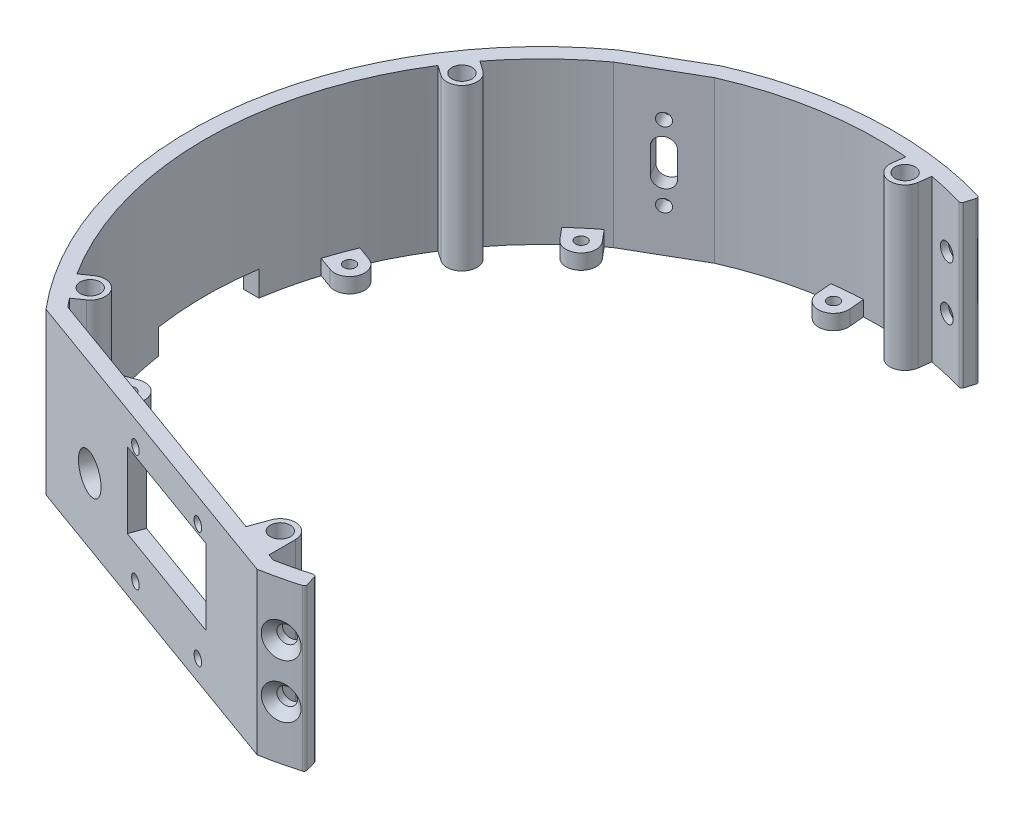
SolidWorks part; units mm, degrees
ref_plane "Front Plane" through (0, 0, 0) normal (0, 0, 1) x (1, 0, 0)
ref_plane "Top Plane" through (0, 0, 0) normal (0, 1, 0) x (1, 0, 0)
ref_plane "Right Plane" through (0, 0, 0) normal (1, 0, 0) x (0, 0, -1)
sketch "Sketch2" plane through (0, 0, 0) normal (0, 1, 0) x (1, 0, 0)
  line L0 (12.3, 68.9109) -> (12.3, -68.9109) construction
  line L1 (12.3, -68.9109) -> (-53.5286, -45.1076)
  line L2 (-28.3033, 64.0228) -> (-41.2937, 56.5228)
  line L3 (-51.7436, -42.5629) -> (12.3, -65.7208)
  line L4 (20.0782, 67.0587) -> (0, 0) construction
  line L5 (0, 0) -> (20.0782, -67.0587) construction
  line L6 (19.2177, 64.1847) -> (20.0782, 67.0587)
  line L7 (20.0782, -67.0587) -> (19.178, -64.0524)
  line L8 (-39.6526, 54.0062) -> (-26.9445, 61.3433)
  line L9 (-34.7985, 60.2728) -> (0, 0) construction
  line L10 (0, 0) -> (0, 50000) construction
  arc A0 (12.3, 68.9109) -> (-28.3033, 64.0228) centre (0, 0) ccw construction
  arc A1 (-53.5286, -45.1076) -> (-41.2937, 56.5228) centre (0, 0) cw
  arc A2 (12.3, 65.8613) -> (-26.9445, 61.3433) centre (0, 0) ccw
  arc A3 (12.3, 68.9109) -> (20.0782, 67.0587) centre (0, 0) cw
  arc A4 (12.3, 65.8613) -> (19.2177, 64.1847) centre (0, 0) cw
  arc A5 (12.3, -68.9109) -> (20.0782, -67.0587) centre (0, 0) ccw
  arc A6 (12.3, -65.7208) -> (19.178, -64.0524) centre (0, 0) ccw
  arc A7 (-39.6526, 54.0062) -> (-51.7436, -42.5629) centre (0, 0) ccw
  arc A8 (-41.2937, 56.5228) -> (12.3, -68.9109) centre (0, 0) ccw construction
  arc A9 (-28.3033, 64.0228) -> (12.3, 68.9109) centre (0, 0) cw
  point P18 (-33.2985, 57.6747)
  dimension "D1" = 70
  dimension "D4" = 3
  dimension "D6" = 8
  dimension "D2" = 12.3
  dimension "D3" = 3
  dimension "D5" = 70
  dimension "D7" = 8
  dimension "D8" = 3
  dimension "D9" = 15
  dimension "D10" = 30
extrude "Boss-Extrude1" add sketch "Sketch2" along normal blind 32
sketch "Sketch3" plane through (0, 0, 0) normal (0, 1, 0) x (1, 0, 0)
  line L0 (12.3, 68.9109) -> (12.3, -68.9109) construction
  line L1 (20.0782, -67.0587) -> (19.178, -64.0524) construction
  line L2 (19.2177, 64.1847) -> (20.0782, 67.0587) construction
  circle A0 centre (0, 0) radius 70 construction
  arc A1 (12.3, -68.9109) -> (20.0782, -67.0587) centre (0, 0) ccw
  arc A2 (12.3, 68.9109) -> (20.0782, 67.0587) centre (0, 0) cw
  point P8 (16.2155, -68.0959)
  point P9 (16.2155, 68.0959)
  dimension "D2" = 140
  dimension "D1" = 12.3
sketch3d "3DSketch1"
  line L0 (16.2155, 0, 68.0959) -> (16.2155, 32, 68.0959)
  line L1 (16.2155, 0, -68.0959) -> (16.2155, 32, -68.0959)
  arc A0 (12.3, 32, 68.9109) -> (20.0782, 32, 67.0587) centre (0, 32, 0) ccw construction
  arc A1 (20.0782, 32, -67.0587) -> (-28.3033, 32, -64.0228) centre (0, 32, 0) ccw construction
  point P6 (0, 102, 0)
  point P13 (0, 102, 0)
  point P14 (16.2155, 21.3333, 68.0959)
  point P15 (16.2155, 10.6667, 68.0959)
  point P16 (16.2155, 10.6667, -68.0959)
  point P17 (16.2155, 21.3333, -68.0959)
  dimension "D1" = 10.6667
  dimension "D2" = 21.3333
  dimension "D3" = 10.6667
  dimension "D4" = 21.3333
ref_plane "Plane1" through (16.2155, 0, -68.0959) normal (0.2317, 0, -0.9728) x (-0.9728, 0, -0.2317)
ref_plane "Plane2" through (16.2155, 0, 68.0959) normal (0.2317, 0, 0.9728) x (0.9728, 0, -0.2317)
sketch "Sketch4" plane through (16.2155, 0, -68.0959) normal (0.2317, 0, -0.9728) x (-0.9728, 0, -0.2317)
  line L0 (0, 0) -> (0, 32) construction
  circle A0 centre (0, 21.3333) radius 1.65 construction
  circle A1 centre (0, 10.6667) radius 1.65 construction
  point P0 (0, 21.3333)
  point P4 (0, 10.6667)
  dimension "D1" = 3.3
  dimension "D2" = 10.6667
  dimension "D3" = 21.3333
sketch "Sketch5" plane through (16.2155, 0, 68.0959) normal (0.2317, 0, 0.9728) x (0.9728, 0, -0.2317)
  line L0 (0, 0) -> (0, 32) construction
  circle A0 centre (0, 21.3333) radius 1.65 construction
  circle A1 centre (0, 10.6667) radius 1.65 construction
  point P0 (0, 21.3333)
  point P4 (0, 10.6667)
  dimension "D1" = 3.3
  dimension "D2" = 10.6667
  dimension "D3" = 21.3333
fillet "Fillet1" radius 0.5 4 edges at (20.0782, 16, -67.0587) (19.2177, 16, -64.1847) (19.178, 16, 64.0524) (20.0782, 16, 67.0587)
sketch "Sketch6" plane through (0, 0, 0) normal (1, 0, 0) x (0, 0, -1)
  line L0 (70, 0) -> (-70, 0) construction
  line L1 (-10, 0) -> (10, 0)
  line L2 (-10, 0) -> (-10, 5)
  line L3 (-10, 5) -> (10, 5)
  line L4 (10, 0) -> (10, 5)
  dimension "D1" = 10
  dimension "D2" = 5
  dimension "D3" = 20
extrude "Cut-Extrude3" cut sketch "Sketch6" against normal through all
sketch "Sketch7" plane through (-20.6143, 0, 57.0092) normal (-0.34, 0, 0.9404) x (0.9404, 0, 0.34)
  line L0 (5, 29.3) -> (5, 2) construction
  line L1 (-8.65, 29.3) -> (18.65, 29.3) construction
  line L2 (-8.65, 29.3) -> (-8.65, 2) construction
  line L3 (-8.65, 2) -> (18.65, 2) construction
  line L4 (18.65, 29.3) -> (18.65, 2) construction
  line L5 (-8.65, 29.3) -> (18.65, 2) construction
  line L6 (-8.65, 2) -> (18.65, 29.3) construction
  line L7 (-35, 0) -> (35, 0) construction
  line L8 (-8.05, 25.58) -> (18.05, 25.58)
  line L9 (-8.05, 25.58) -> (-8.05, 10.58)
  line L10 (-8.05, 10.58) -> (18.05, 10.58)
  line L11 (18.05, 25.58) -> (18.05, 10.58)
  line L12 (-8.05, 25.58) -> (18.05, 10.58) construction
  line L13 (-8.05, 10.58) -> (18.05, 25.58) construction
  line L14 (-5.35, 27.25) -> (15.35, 27.25) construction
  line L15 (-5.35, 27.25) -> (-5.35, 4.05) construction
  line L16 (-5.35, 4.05) -> (15.35, 4.05) construction
  line L17 (15.35, 27.25) -> (15.35, 4.05) construction
  line L18 (70, 0) -> (-70, 0) construction
  circle A0 centre (-5.35, 27.25) radius 1.25
  circle A1 centre (15.35, 27.25) radius 1.25
  circle A2 centre (15.35, 4.05) radius 1.25
  circle A3 centre (-5.35, 4.05) radius 1.25
  circle A4 centre (-20.5, 13) radius 3.75
  point P0 (5, 15.65)
  point P5 (5, 18.08)
  point P24 (0, 0)
  dimension "D9" = 2.5
  dimension "D13" = 7.5
  dimension "D14" = 13
  dimension "D15" = 20.5
  dimension "D1" = 27.3
  dimension "D2" = 27.3
  dimension "D3" = 26.1
  dimension "D4" = 15
  dimension "D5" = 2.05
  dimension "D6" = 3.3
  dimension "D7" = 20.7
  dimension "D8" = 11.22
  dimension "D10" = 5
  dimension "D11" = 2
  dimension "D12" = 23.2
extrude "Cut-Extrude4" cut sketch "Sketch7" against normal blind 8
sketch "Sketch8" plane through (0, 0, 0) normal (0, 1, 0) x (1, 0, 0)
  line L0 (8.7453, 66.4268) -> (8.4189, 63.9482) construction
  line L1 (11.7108, 65.9686) -> (11.3933, 63.5566)
  line L2 (5.7621, 66.7518) -> (5.4446, 64.3398)
  line L3 (5.4446, 64.3398) -> (11.3933, 63.5566) construction
  line L4 (-54.8832, 38.4296) -> (-52.8353, 36.9957) construction
  line L5 (-53.1074, 40.8485) -> (-51.1146, 39.4531)
  line L6 (-56.5489, 35.9336) -> (-54.556, 34.5382)
  line L7 (-54.556, 34.5382) -> (-51.1146, 39.4531) construction
  line L8 (-54.8832, -38.4296) -> (-52.8353, -36.9957) construction
  line L9 (-56.5489, -35.9336) -> (-54.556, -34.5382)
  line L10 (-53.1074, -40.8485) -> (-51.1146, -39.4531)
  line L11 (-51.1146, -39.4531) -> (-54.556, -34.5382) construction
  line L12 (0, 1.3173) -> (0, 50001.3173) construction
  line L13 (11, -65.2507) -> (11, -60)
  line L14 (12.3, -65.7208) -> (-51.7436, -42.5629) construction
  line L15 (5.1788, -58.9799) -> (3.8466, -62.6641)
  line L16 (8, -60) -> (6.6678, -63.6842) construction
  line L17 (11, -65.2507) -> (3.8466, -62.6641)
  arc A0 (-53.1074, -40.8485) -> (-56.5489, -35.9336) centre (0, 0) cw
  arc A1 (18.7417, 64.3253) -> (-26.9445, 61.3433) centre (0, 0) ccw construction
  arc A2 (5.7621, 66.7518) -> (11.7108, 65.9686) centre (0, 0) cw
  circle A3 centre (8.4189, 63.9482) radius 1.65
  arc A4 (11.3933, 63.5566) -> (5.4446, 64.3398) centre (8.4189, 63.9482) cw
  arc A5 (-56.5489, 35.9336) -> (-53.1074, 40.8485) centre (0, 0) cw
  circle A6 centre (-52.8353, 36.9957) radius 1.65
  arc A7 (-51.1146, 39.4531) -> (-54.556, 34.5382) centre (-52.8353, 36.9957) cw
  circle A8 centre (-52.8353, -36.9957) radius 1.65
  arc A9 (-54.556, -34.5382) -> (-51.1146, -39.4531) centre (-52.8353, -36.9957) cw
  arc A10 (11, -60) -> (5.1788, -58.9799) centre (8, -60) ccw
  circle A11 centre (8, -60) radius 1.65
  circle A12 centre (0, 0) radius 67 construction
  point P12 (8.7453, 66.4268)
  point P15 (8.7453, 66.4268)
  point P17 (8.4189, 63.9482)
  point P24 (-54.8832, 38.4296)
  point P26 (-54.8832, 38.4296)
  point P27 (-52.8353, 36.9957)
  point P43 (-52.8353, -36.9957)
  dimension "D1" = 3.3
  dimension "D2" = 6
  dimension "D3" = 3.3
  dimension "D5" = 3.3
  dimension "D13" = 3
  dimension "D14" = 3.3
  dimension "D4" = 6
  dimension "D6" = 6
  dimension "D7" = 2.5
  dimension "D8" = 7.5
  dimension "D9" = 55
  dimension "D10" = 55
  dimension "D11" = 2.5
  dimension "D12" = 2.5
  dimension "D15" = 60
  dimension "D16" = 8
extrude "Boss-Extrude2" add sketch "Sketch8" along normal up to surface (32 mm away) up to face at (-6.541, 32, -1.7)
sketch "Sketch13" plane through (0, 0, 0) normal (0, 1, 0) x (1, 0, 0)
  line L0 (-62.8963, 22.8924) -> (-60.0772, 21.8663) construction
  line L1 (-59.0511, 24.6854) -> (-61.1032, 19.0472) construction
  line L2 (-61.1032, 19.0472) -> (-63.9223, 20.0733)
  line L3 (-61.8702, 25.7114) -> (-59.0511, 24.6854)
  line L4 (0, 0) -> (0, 50000) construction
  line L5 (-62.8963, -22.8924) -> (-60.0772, -21.8663) construction
  line L6 (-61.1032, -19.0472) -> (-59.0511, -24.6854) construction
  line L7 (-59.0511, -24.6854) -> (-61.8702, -25.7114)
  line L8 (-63.9223, -20.0733) -> (-61.1032, -19.0472)
  line L9 (-5.8336, 66.6781) -> (-5.5721, 63.6895) construction
  line L10 (-2.5835, 63.951) -> (-8.5607, 63.4281) construction
  line L11 (-8.5607, 63.4281) -> (-8.8222, 66.4166)
  line L12 (-2.845, 66.9396) -> (-2.5835, 63.951)
  line L13 (-43.0236, 51.2735) -> (-41.0952, 48.9754) construction
  line L14 (-38.7971, 50.9037) -> (-43.3933, 47.047) construction
  line L15 (-43.3933, 47.047) -> (-45.3217, 49.3451)
  line L16 (-40.7254, 53.2019) -> (-38.7971, 50.9037)
  line L17 (1.0254, -61.6439) -> (2.0455, -58.8227) construction
  line L18 (-0.7757, -57.8026) -> (4.8667, -59.8428) construction
  line L19 (4.8667, -59.8428) -> (3.8466, -62.6641)
  line L20 (-1.7959, -60.6238) -> (-0.7757, -57.8026)
  line L21 (3.8466, -62.6641) -> (-1.7959, -60.6238)
  line L22 (5.1788, -58.9799) -> (3.8466, -62.6641) construction
  line L25 (3.8466, -62.6641) -> (-51.7436, -42.5629) construction
  circle A0 centre (0, 0) radius 67 construction
  arc A1 (-63.9223, 20.0733) -> (-61.8702, 25.7114) centre (0, 0) cw
  arc A2 (-61.1032, 19.0472) -> (-59.0511, 24.6854) centre (-60.0772, 21.8663) ccw
  circle A3 centre (-60.0772, 21.8663) radius 1.15
  arc A4 (-61.8702, -25.7114) -> (-63.9223, -20.0733) centre (0, 0) cw
  arc A5 (-59.0511, -24.6854) -> (-61.1032, -19.0472) centre (-60.0772, -21.8663) ccw
  circle A6 centre (-60.0772, -21.8663) radius 1.15
  arc A7 (-8.8222, 66.4166) -> (-2.845, 66.9396) centre (0, 0) cw
  arc A8 (-8.5607, 63.4281) -> (-2.5835, 63.951) centre (-5.5721, 63.6895) ccw
  circle A9 centre (-5.5721, 63.6895) radius 1.15
  arc A10 (-45.3217, 49.3451) -> (-40.7254, 53.2019) centre (0, 0) cw
  arc A11 (-43.3933, 47.047) -> (-38.7971, 50.9037) centre (-41.0952, 48.9754) ccw
  circle A12 centre (-41.0952, 48.9754) radius 1.15
  arc A14 (4.8667, -59.8428) -> (-0.7757, -57.8026) centre (2.0455, -58.8227) ccw
  circle A15 centre (2.0455, -58.8227) radius 1.15
  point P10 (-60.0772, 21.8663)
  point P20 (-60.0772, -21.8663)
  point P30 (-5.5721, 63.6895)
  point P41 (-41.0952, 48.9754)
  point P52 (2.0455, -58.8227)
  dimension "D1" = 134
  dimension "D2" = 3
  dimension "D3" = 2.3
  dimension "D6" = 3
  dimension "D7" = 2.3
  dimension "D10" = 3
  dimension "D11" = 2.3
  dimension "D14" = 3
  dimension "D15" = 2.3
  dimension "D18" = 3
  dimension "D19" = 2.3
  dimension "D4" = 3
  dimension "D5" = 70
  dimension "D8" = 3
  dimension "D9" = 70
  dimension "D12" = 3
  dimension "D13" = 5
  dimension "D16" = 3
  dimension "D17" = 40
  dimension "D20" = 3
  dimension "D21" = 2.0455
  dimension "D22" = 58.8227
extrude "Boss-Extrude3" add sketch "Sketch13" along normal blind 3
hole_wizard "CSK for M3 Flat Head Machine Screw1" positions "Sketch4" profile "Sketch16" countersink size "M3" standard "ANSI Metric"
sketch "Sketch16" plane through (16.2155, 21.3333, -68.0959) normal (0, 1, 0) x (-0.9728, 0, -0.2317)
  line L0 (0, 0) -> (0, 21.0215)
  line L1 (0, 21.0215) -> (1.7, 20)
  line L2 (1.7, 20) -> (1.7, 1.675)
  line L3 (1.7, 1.675) -> (3.375, 0)
  line L5 (3.375, 0) -> (0, 0)
  line L6 (-1.7, 1.675) -> (-3.375, 0) construction
  line L10 (0, 21.0215) -> (-1.7, 20) construction
  line L11 (0, -6.35) -> (0, 107.95) construction
  dimension "Hole Dia." = 3.4
  dimension "Hole Depth" = 20
  dimension "Near C'Sink Dia." = 6.75
  dimension "Near C'Sink Angle" = 90
  dimension "Drill Angle" = 118
hole_wizard "CSK for M3 Flat Head Machine Screw2" positions "Sketch5" profile "Sketch17" countersink size "M3" standard "ANSI Metric"
sketch "Sketch17" plane through (16.2155, 21.3333, 68.0959) normal (0, 1, 0) x (0.9728, 0, -0.2317)
  line L0 (0, 0) -> (0, 21.0215)
  line L1 (0, 21.0215) -> (1.7, 20)
  line L2 (1.7, 20) -> (1.7, 1.675)
  line L3 (1.7, 1.675) -> (3.375, 0)
  line L5 (3.375, 0) -> (0, 0)
  line L6 (-1.7, 1.675) -> (-3.375, 0) construction
  line L10 (0, 21.0215) -> (-1.7, 20) construction
  line L11 (0, -6.35) -> (0, 107.95) construction
  dimension "Hole Dia." = 3.4
  dimension "Hole Depth" = 20
  dimension "Near C'Sink Dia." = 6.75
  dimension "Near C'Sink Angle" = 90
  dimension "Drill Angle" = 118
sketch "Sketch18" plane through (0, 32, 0) normal (0, 1, 0) x (1, 0, 0)
  circle A0 centre (8.4189, 63.9482) radius 2
  circle A1 centre (-52.8353, 36.9957) radius 2
  circle A2 centre (-52.8353, -36.9957) radius 2
  circle A3 centre (8, -60) radius 2
  dimension "D1" = 4
extrude "Cut-Extrude5" cut sketch "Sketch18" against normal blind 4.78
sketch "Sketch19" plane through (-34.7985, 0, -60.2728) normal (-0.5, 0, -0.866) x (-0.866, 0, 0.5)
  line L0 (0, 23.41) -> (0, 8.59) construction
  line L1 (0, 18.5) -> (0, 13.5) construction
  line L2 (2, 18.5) -> (2, 13.5)
  line L3 (-2, 18.5) -> (-2, 13.5)
  circle A0 centre (0, 23.41) radius 1.25
  circle A1 centre (0, 8.59) radius 1.25
  arc A2 (2, 18.5) -> (-2, 18.5) centre (0, 18.5) ccw
  arc A3 (-2, 13.5) -> (2, 13.5) centre (0, 13.5) ccw
  point P5 (0, 16)
  point P8 (0, 16)
  point P13 (0, 16)
  dimension "D3" = 2.5
  dimension "D4" = 5
  dimension "D5" = 2
  dimension "D1" = 14.82
  dimension "D2" = 16
extrude "Cut-Extrude6" cut sketch "Sketch19" against normal blind 10
